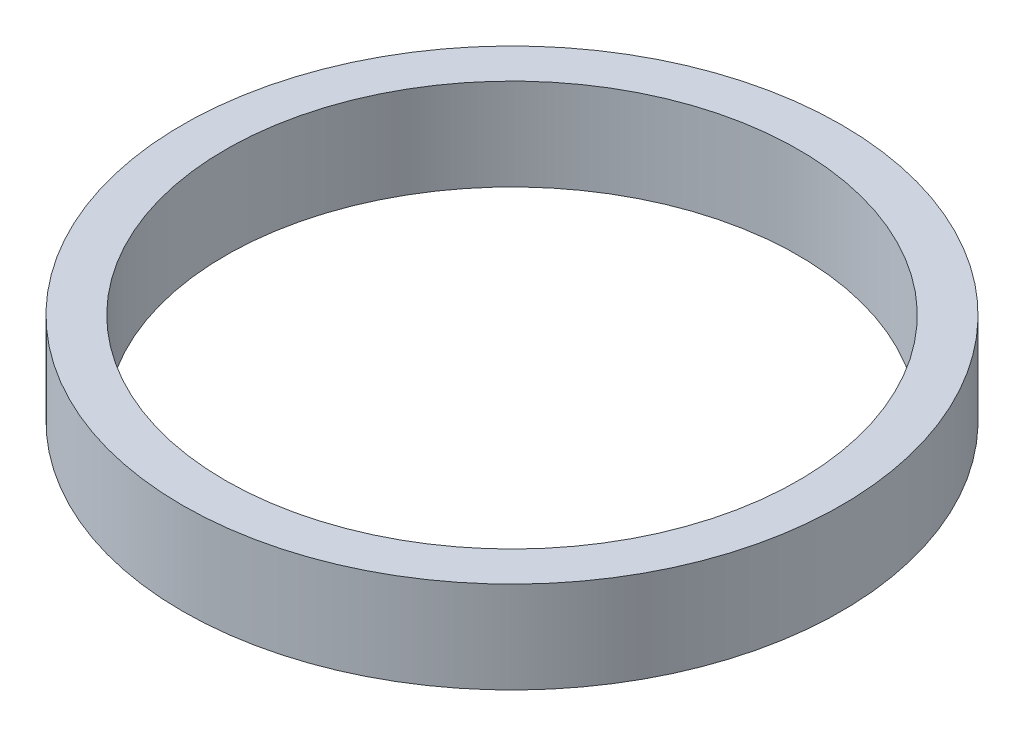
SolidWorks part; units mm, degrees
ref_plane "Front Plane" through (0, 0, 0) normal (0, 0, 1) x (1, 0, 0)
ref_plane "Top Plane" through (0, 0, 0) normal (0, 1, 0) x (1, 0, 0)
ref_plane "Right Plane" through (0, 0, 0) normal (1, 0, 0) x (0, 0, -1)
sketch "Sketch1" plane through (0, 0, 0) normal (0, 1, 0) x (1, 0, 0)
  circle A0 centre (0, 0) radius 57.5
  dimension "FLANGE_OD" = 115
extrude "Boss-Extrude1" add sketch "Sketch1" along normal blind 16
sketch "Sketch2" plane through (0, 0, 0) normal (0, 1, 0) x (1, 0, 0)
  circle A0 centre (0, 0) radius 50
  dimension "BORE_D" = 100
extrude "Cut-Extrude1" cut sketch "Sketch2" along normal through all
sketch "Sketch3" plane through (0, 16, 0) normal (0, 1, 0) x (1, 0, 0)
  circle A0 centre (0, 0) radius 26.8131 construction
  circle A1 centre (-26.8131, 0) radius 1.5
  dimension "BOLT_D" = 3
  dimension "BOLT_PCD" = 53.6262
extrude "Cut-Extrude2" cut sketch "Sketch3" against normal blind 12.0245 rebuild error yes
pattern_circular "CirPattern1" count 4 over 360 rebuild error yes
